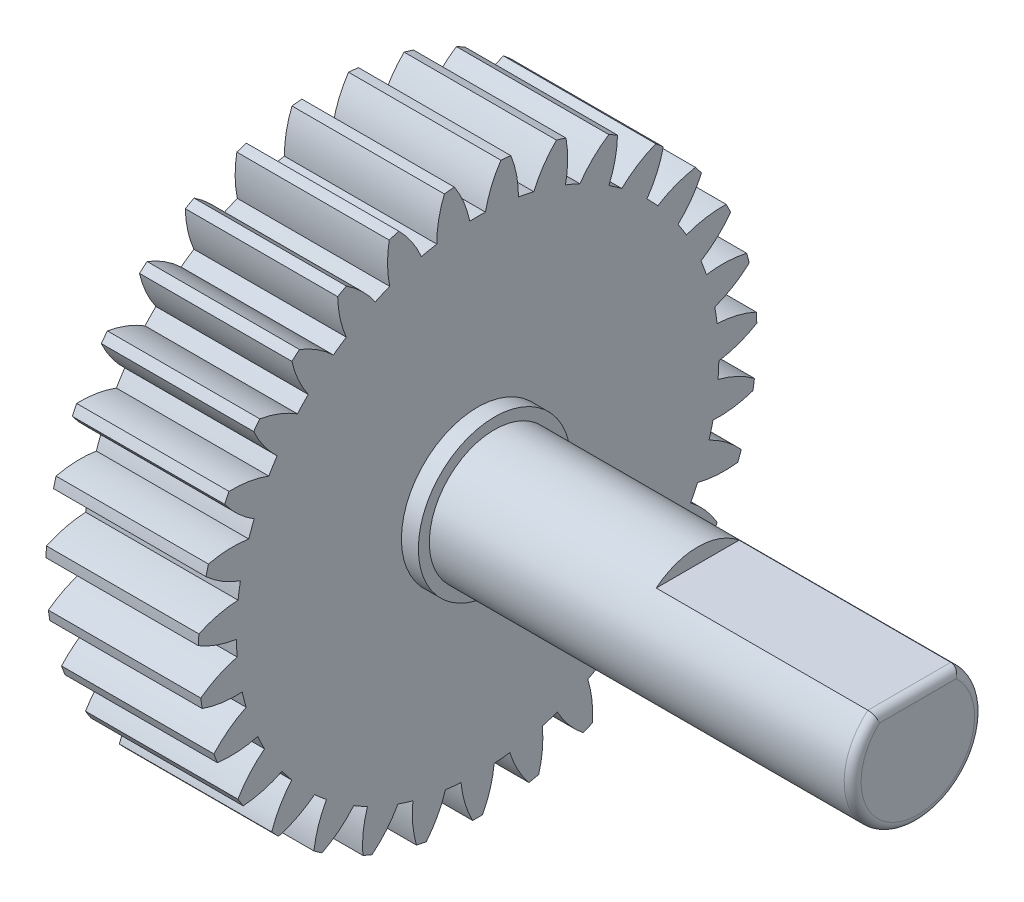
SolidWorks part; units mm, degrees
ref_plane "Plane1" through (0, 0, 0) normal (0, 0, 1) x (1, 0, 0)
ref_plane "Plane2" through (0, 0, 0) normal (0, 1, 0) x (1, 0, 0)
ref_plane "Plane3" through (0, 0, 0) normal (1, 0, 0) x (0, 0, -1)
sketch "HoldingSke" plane through (0, 0, 0) normal (0, 1, 0) x (1, 0, 0)
  line L0 (0, 0) -> (0.8572, -0.515)
  line L1 (-15, 0) -> (100, 0) construction
  line L2 (0, 0) -> (-2.1039, 2.3779)
  line L3 (0, 0) -> (-11.863, 4.5341)
  line L4 (0, 0) -> (7.4025, 4.4479)
  line L5 (0, 0) -> (-46.8476, -17.4728)
  line L6 (0, 0) -> (-7.4607, -5.0337)
  line L7 (-2.1039, 2.3779) -> (8.6586, 51.2059)
  line L8 (-76.2, 54.61) -> (-75.5, 54.61)
  line L9 (-71.009, 38.7566) -> (-53.1078, 45.2721)
  line L10 (-76.2, 71.12) -> (104.1128, 71.12)
  line L11 (0, 0) -> (-9, 0)
  line L12 (-76.2, 101.6) -> (-76.162, 101.6)
  line L13 (24.9733, 27.94) -> (52.9518, 28.4284)
  line L14 (24.9733, 27.94) -> (24.9743, 27.94)
  line L15 (24.9733, 27.94) -> (100.4006, 29.5858)
  line L16 (-63.627, -1) -> (-12.827, -1)
  circle A0 centre (0, 0) radius 2
  circle A1 centre (0, 0) radius 14.249
  circle A2 centre (0, 0) radius 37.5
  circle A3 centre (0, 0) radius 2
  dimension "MHD" = 28.498
  dimension "Hub_dia" = 75
  dimension "Bore" = 4
  dimension "MBD" = 4
  dimension "Num_teeth" = 31
  dimension "Pitch" = 1
  dimension "Overall_len" = 50
  dimension "Show_teeth" = 31
  dimension "Thickness" = 9
  dimension "OAL" = 50.0001
  dimension "T_dim" = 0.7
  dimension "Ap" = 20
  dimension "H" = 19.05
  dimension "Pitch_radius" = 180.3128
  dimension "Width" = 9
  dimension "Backlash" = 0.038
  dimension "Addendum_fac" = 1
  dimension "Dedendum_fac" = 1.25
  dimension "Clearance_fac" = 0.25
  dimension "Dedendum_add" = 0.001
  dimension "Module" = 1
sketch "BasProSke" plane through (0, 0, 0) normal (0, 1, 0) x (1, 0, 0)
  line L0 (-10, 0) -> (60, 0) construction
  line L1 (0, 0) -> (0, 16.5)
  line L2 (0, 0) -> (9, 0)
  line L3 (9, 0) -> (9, 16.5)
  line L4 (9, 16.5) -> (0, 16.5)
  dimension "Thickness" = 9
  dimension "Diameter" = 33
revolve "Base-Revolve" add sketch "BasProSke" angle 360 about L0
sketch "TooCutSke" plane through (0, 0, 0) normal (1, 0, 0) x (0, 0, -1)
  line L1 (0, 0) -> (0, 107) construction
  line L2 (0, 0) -> (-0.8515, 15.4766) construction
  line L3 (0, 0) -> (-3.1328, 30.8078) construction
  line L4 (-0.8515, 15.4766) -> (-1.5664, 15.4039) construction
  arc A0 (0.4642, 14.2414) -> (-0.4642, 14.2414) centre (0, 0) ccw
  arc A1 (1.3919, 16.4667) -> (-1.3919, 16.4667) centre (0, 0) ccw
  circle A2 centre (0, 0) radius 15.5 construction
  circle A3 centre (0, 0) radius 14.5652 construction
  arc A4 (-0.4642, 14.2414) -> (-1.3919, 16.4667) centre (-6.5414, 13.0137) ccw
  arc A5 (1.3919, 16.4667) -> (0.4642, 14.2414) centre (6.5414, 13.0137) ccw
  dimension "Root_dia" = 28.498
  dimension "Overcut_dia" = 33.0508
  dimension "Pitch_dia" = 31
  dimension "Base_dia" = 29.1305
  dimension "Flank_rad" = 6.2
  dimension "Half_ang" = 5.806
  dimension "Half_CT" = 0.7186
extrude "ToothCut" cut sketch "TooCutSke" along normal through all
fillet "Breaks" [suppressed] radius 0.02 tangent propagation no
fillet "RootFillets" [suppressed] radius 0.251
pattern_circular "TeethCuts" count 31 every 11.613 about axis through (-10, 0, 0) along (1, 0, 0) of "ToothCut", "RootFillets", "Breaks"
sketch "HubNeaOneSke" plane through (0, 0, 0) normal (-1, 0, 0) x (0, 0, 1)
  circle A0 centre (0, 0) radius 14.249
  dimension "Diameter" = 28.498
extrude "HubNearOne" [suppressed] add sketch "HubNeaOneSke" along normal blind 41.0001
sketch "HubNeaBotSke" plane through (0, 0, 0) normal (-1, 0, 0) x (0, 0, 1)
  circle A0 centre (0, 0) radius 14.249
  dimension "Diameter" = 28.498
extrude "HubNearBoth" [suppressed] add sketch "HubNeaBotSke" along normal blind 20.5
ref_plane "FarPln" through (9, 0, 0) normal (1, 0, 0) x (0, 0, -1)
sketch "HubFarSke" plane through (9, 0, 0) normal (1, 0, 0) x (0, 0, -1)
  circle A0 centre (0, 0) radius 14.249
  dimension "Diameter" = 28.498
extrude "HubFar" [suppressed] add sketch "HubFarSke" along normal blind 20.5
sketch "BorSke" plane through (0, 0, 0) normal (1, 0, 0) x (0, 0, -1)
  circle A0 centre (0, 0) radius 2
  dimension "Diameter" = 4
extrude "Bore" cut sketch "BorSke" along normal mid plane 100.0001
sketch "KeySke" plane through (0, 0, 0) normal (1, 0, 0) x (0, 0, -1)
  line L0 (-0.8, 0) -> (-0.8, 2.7)
  line L1 (-0.8, 2.7) -> (0.8, 2.7)
  line L2 (0.8, 2.7) -> (0.8, 0)
  line L3 (0, 0) -> (0, 34) construction
  line L4 (-0.8, 0) -> (0.8, 0)
  dimension "Offset" = 2.7
  dimension "Width" = 1.6
extrude "Keyway" [suppressed] cut sketch "KeySke" along normal mid plane 100.0001
pattern_circular "Keyway2" [suppressed] count 2 every 90 about axis through (-10, 0, 0) along (1, 0, 0) reverse direction yes
sketch "Sketch2" plane through (9, 0, 0) normal (1, 0, 0) x (0, 0, -1)
  line L0 (-2.45, 2.9698) -> (2.45, 2.9698)
  circle A0 centre (0, 0) radius 3.85
  circle A1 centre (0, 0) radius 4.5
  dimension "D1" = 7.7
  dimension "D2" = 9
  dimension "D3" = 4.9
extrude "Boss-Extrude1" add sketch "Sketch2" along normal blind 1 contours A1 A0 region at (9, 0, 4.3727)
extrude "Boss-Extrude2" add sketch "Sketch2<3>" along normal blind 26 and the other way blind 9 contours L0 A0 region at (9, -0.2248, 0)
sketch "Sketch2<3>" plane through (9, 0, 0) normal (1, 0, 0) x (0, 0, -1) same geometry as "Sketch2"
extrude "Boss-Extrude3" add sketch "Sketch2<4>" along normal blind 13 and the other way blind 9 contours L0 A0 region at (9, 3.3256, 0)
sketch "Sketch2<4>" plane through (9, 0, 0) normal (1, 0, 0) x (0, 0, -1) same geometry as "Sketch2"
fillet "Fillet1" radius 0.5 2 edges at (35, 2.9698, 0) (35, -3.85, 0)
equation "' \"Module@HoldingSke\" = 6.35"
equation "' \"Num_teeth@HoldingSke\" = 12"
equation "' \"Ap@HoldingSke\" =  20"
equation "' \"Ap@HoldingSke\" = 20"
equation "' \"Width@HoldingSke\" = 0.5 * 25.4"
equation "' \"Hub_dia@HoldingSke\"= 1 * 25.4"
equation "' \"Hub_dia@HoldingSke\" = 1 * 25.4"
equation "' \"Overall_len@HoldingSke\" = 1.0 * 25.4"
equation "' \"Bore@HoldingSke\" = 0.75 * 25.4"
equation "' \"T_dim@HoldingSke\" = 0.1 * 25.4"
equation "' \"Width@KeySke\" = 0.25 * 25.4"
equation "' \"Show_teeth@HoldingSke\" = 13"
equation "' \"Backlash@HoldingSke\" = 0.009 * 25.4"
equation "' \"Addendum_fac@HoldingSke\" = 1.0"
equation "' \"Dedendum_fac@HoldingSke\" = 1.25"
equation "' \"Dedendum_add@HoldingSke\" = 0.00005 * 25.4"
equation "' \"Clearance_fac@HoldingSke\" = 0.25"
equation "\"Pitch@HoldingSke\" = 1 / \"Module@HoldingSke\""
equation "\"Overcut_dia@TooCutSke\" = (\"Num_teeth@HoldingSke\" + 2 * \"Addendum_fac@HoldingSke\") / \"Pitch@HoldingSke\" + 0.002 * 25.4"
equation "\"Pitch_dia@TooCutSke\" = \"Num_teeth@HoldingSke\" / \"Pitch@HoldingSke\""
equation "\"Base_dia@TooCutSke\" = \"Num_teeth@HoldingSke\" / \"Pitch@HoldingSke\" * cos((\"Ap@HoldingSke\"  * 3.14159265 / 180))"
equation "\"Root_dia@TooCutSke\" = (\"Num_teeth@HoldingSke\" + 2) / \"Pitch@HoldingSke\" - 2 * (\"Addendum_fac@HoldingSke\" + \"Dedendum_fac@HoldingSke\") / \"Pitch@HoldingSke\" - \"Dedendum_add@HoldingSke\" * 2"
equation "\"Half_ang@TooCutSke\" = 180 / \"Num_teeth@HoldingSke\""
equation "\"Half_CT@TooCutSke\" = \"Num_teeth@HoldingSke\" / \"Pitch@HoldingSke\" * sin((3.14159265 / 2 / \"Num_teeth@HoldingSke\")) / 2 - 7 * \"Backlash@HoldingSke\" / 4"
equation "\"Flank_rad@TooCutSke\" = \"Num_teeth@HoldingSke\" / \"Pitch@HoldingSke\" / 5"
equation "\"Radius@RootFillets\" = \"Clearance_fac@HoldingSke\" / \"Pitch@HoldingSke\" + \"Dedendum_add@HoldingSke\""
equation "\"Break_rad@Breaks\" = 0.02 / \"Pitch@HoldingSke\""
equation "\"Thickness@HoldingSke\" = \"Width@HoldingSke\""
equation "\"OAL@HoldingSke\" = \"Thickness@HoldingSke\""
equation "\"MHD@HoldingSke\" = (\"Num_teeth@HoldingSke\" + 2) / \"Pitch@HoldingSke\" - 2 * (\"Addendum_fac@HoldingSke\" + \"Dedendum_fac@HoldingSke\")  / \"Pitch@HoldingSke\" - \"Dedendum_add@HoldingSke\" * 2"
equation "\"MBD@HoldingSke\" = (\"Num_teeth@HoldingSke\" + 2) / \"Pitch@HoldingSke\" - 2 * (\"Addendum_fac@HoldingSke\" + \"Dedendum_fac@HoldingSke\")  / \"Pitch@HoldingSke\" - \"Dedendum_add@HoldingSke\" * 2 - 0.002 * 25.4"
equation "\"MHD@HoldingSke\" = ((sgn( \"MHD@HoldingSke\" - \"Hub_dia@HoldingSke\" )-1)*( \"MHD@HoldingSke\" - \"Hub_dia@HoldingSke\" ))/-2+ \"Hub_dia@HoldingSke\""
equation "\"MBD@HoldingSke\" = ((sgn( \"MBD@HoldingSke\" - \"Bore@HoldingSke\" )-1)*( \"MBD@HoldingSke\" - \"Bore@HoldingSke\" ))/-2+ \"Bore@HoldingSke\""
equation "\"OAL@HoldingSke\" = ((sgn( \"OAL@HoldingSke\" - \"Overall_len@HoldingSke\" )+1)*( \"OAL@HoldingSke\" - \"Overall_len@HoldingSke\" ))/2 + \"Overall_len@HoldingSke\" + 0.000002 * 25.4"
equation "\"Num_teeth@TeethCuts\" = int( \"Show_teeth@HoldingSke\" ) + 1"
equation "\"Num_teeth@TeethCuts\" = ((sgn( \"Num_teeth@TeethCuts\" - \"Num_teeth@HoldingSke\" )-1)*( \"Num_teeth@TeethCuts\" - \"Num_teeth@HoldingSke\" ))/-2+ \"Num_teeth@HoldingSke\""
equation "\"Num_teeth@TeethCuts\" = ((sgn( \"Num_teeth@TeethCuts\" - 2.0)+1)*( \"Num_teeth@TeethCuts\" - 2.0))/2 +2.0"
equation "\"Angle@TeethCuts\" = 360.0 / \"Num_teeth@HoldingSke\""
equation "\"Diameter@BasProSke\" = (\"Num_teeth@HoldingSke\" + 2 * \"Addendum_fac@HoldingSke\") / \"Pitch@HoldingSke\""
equation "\"Thickness@BasProSke\"  = \"Thickness@HoldingSke\""
equation "' \"Fillet_rad@BasProSke\" =  \"Thickness@HoldingSke\" * 0.05"
equation "' \"Fillet_rad@BasProSke\" = \"Thickness@HoldingSke\" * 0.05"
equation "\"MHD@HoldingSke\" = ((sgn( \"MHD@HoldingSke\" - \"Root_dia@TooCutSke\" )-1)*( \"MHD@HoldingSke\" - \"Root_dia@TooCutSke\" ))/-2+ \"Root_dia@TooCutSke\""
equation "\"Diameter@HubNeaOneSke\" = \"MHD@HoldingSke\""
equation "\"Length@HubNearOne\" = \"OAL@HoldingSke\" - \"Thickness@BasProSke\""
equation "\"Diameter@HubNeaBotSke\" = \"MHD@HoldingSke\""
equation "\"Length@HubNearBoth\" = ( \"OAL@HoldingSke\" - \"Thickness@BasProSke\" ) / 2.0"
equation "\"Thickness@FarPln\" = \"Thickness@BasProSke\""
equation "\"Diameter@HubFarSke\" = \"MHD@HoldingSke\""
equation "\"Length@HubFar\" = ( \"OAL@HoldingSke\" - \"Thickness@BasProSke\" ) / 2.0"
equation "\"Diameter@BorSke\" = \"MBD@HoldingSke\""
equation "\"D1@Bore\" = \"OAL@HoldingSke\" * 2.0"
equation "\"D1@Keyway\" = \"OAL@HoldingSke\" * 2.0"
equation "\"Offset@KeySke\" = \"T_dim@HoldingSke\" + \"MBD@HoldingSke\" / 2.0"
